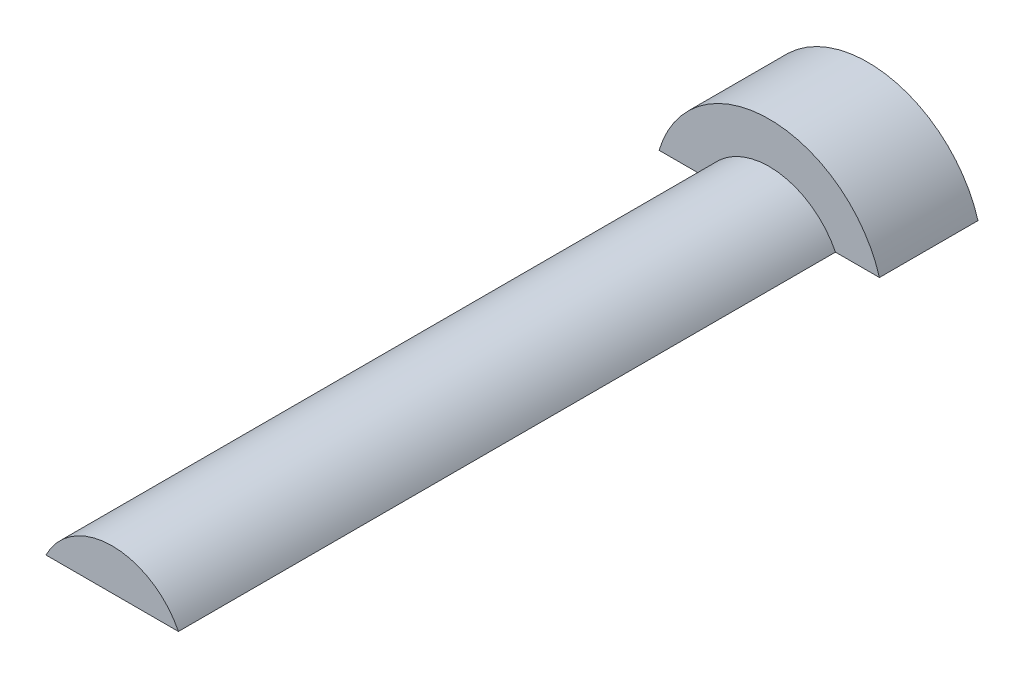
SolidWorks part; units mm, degrees
ref_plane "Front Plane" through (0, 0, 0) normal (0, 0, 1) x (1, 0, 0)
ref_plane "Top Plane" through (0, 0, 0) normal (0, 1, 0) x (1, 0, 0)
ref_plane "Right Plane" through (0, 0, 0) normal (1, 0, 0) x (0, 0, -1)
sketch "Sketch1" plane through (0, 0, 0) normal (0, 0, 1) x (1, 0, 0)
  line L0 (-3.4737, 1) -> (4.1684, 1)
  circle A0 centre (0, 0) radius 3.5
  dimension "D2" = 7
  dimension "D1" = 1
extrude "Boss-Extrude1" add sketch "Sketch1" along normal blind 3 contours L0 A0 region at (0, 2.0388, 0)
sketch "Sketch2" plane through (0, 0, 3) normal (0, 0, 1) x (1, 0, 0)
  line L0 (-3.3541, 1) -> (3.3541, 1)
  circle A0 centre (0, 0) radius 2.25
  dimension "D1" = 4.5
extrude "Boss-Extrude2" add sketch "Sketch2" along normal blind 20 contours L0 A0 region at (0, 1.5142, 3)
